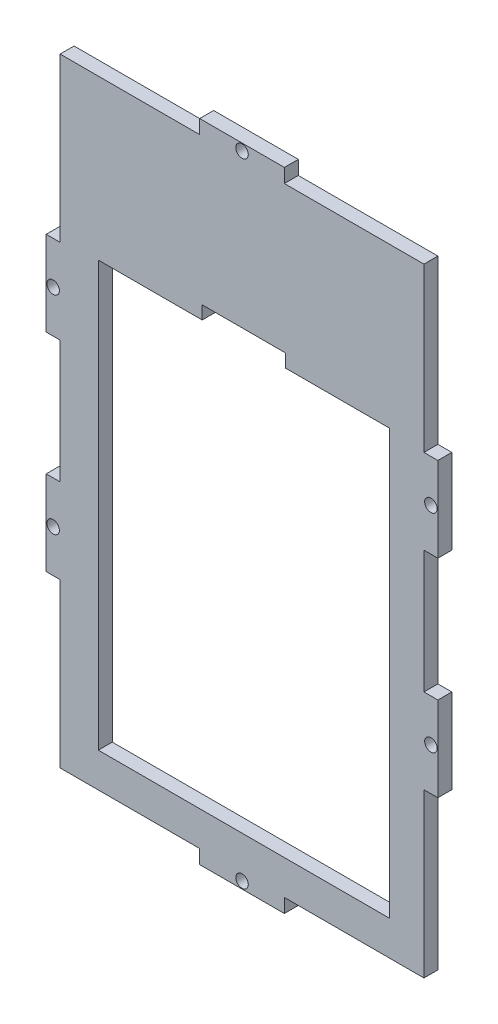
SolidWorks part; units mm, degrees
ref_plane "Front Plane" through (0, 0, 0) normal (0, 0, 1) x (1, 0, 0)
ref_plane "Top Plane" through (0, 0, 0) normal (0, 1, 0) x (1, 0, 0)
ref_plane "Right Plane" through (0, 0, 0) normal (1, 0, 0) x (0, 0, -1)
sketch "Sketch1" plane through (0, 0, 0) normal (0, 0, 1) x (1, 0, 0)
  line L0 (-41.465, 70.465) -> (-13.8217, 70.465)
  line L1 (-41.465, -70.465) -> (41.465, -70.465)
  line L2 (-41.465, -70.465) -> (-41.465, 70.465)
  line L3 (-41.465, 70.465) -> (41.465, 70.465) construction
  line L4 (41.465, -70.465) -> (41.465, 70.465)
  line L5 (-41.465, -70.465) -> (41.465, 70.465) construction
  line L6 (-41.465, 70.465) -> (41.465, -70.465) construction
  line L7 (-13.8217, 70.465) -> (13.8217, 70.465)
  line L8 (13.8217, 70.465) -> (41.465, 70.465)
  point P0 (0, 0)
  dimension "D1" = 82.93
  dimension "D2" = 140.93
extrude "Boss-Extrude1" add sketch "Sketch1" along normal blind 3.18
sketch "Sketch3" plane through (0, 0, 0) normal (0, 0, -1) x (-1, 0, 0)
  line L0 (-33.5967, 34.1533) -> (-33.5967, -62.5967)
  line L1 (-33.5967, -62.5967) -> (32.7533, -62.5967)
  line L2 (32.7533, -62.5967) -> (32.7533, 34.1533)
  line L3 (32.7533, 34.1533) -> (9.0783, 34.1533)
  line L4 (9.0783, 34.1533) -> (9.0783, 37.1533)
  line L5 (9.0783, 37.1533) -> (-9.9217, 37.1533)
  line L6 (-9.9217, 37.1533) -> (-9.9217, 34.1533)
  line L7 (-9.9217, 34.1533) -> (-33.5967, 34.1533)
  line L8 (32.7533, 43.1533) -> (-33.5967, 43.1533)
  line L9 (32.7533, -62.5967) -> (32.7533, 43.1533)
  line L10 (-33.5967, -62.5967) -> (32.7533, -62.5967)
  line L11 (-33.5967, 43.1533) -> (-33.5967, -62.5967)
  line L12 (-33.5967, -62.5967) -> (-33.5967, -70.465) construction
  line L13 (41.465, -70.465) -> (-41.465, -70.465) construction
  line L14 (-33.5967, -62.5967) -> (-41.465, -62.5967) construction
  line L15 (-41.465, -70.465) -> (-41.465, 70.465) construction
  dimension "D1" = 66.35
  dimension "D2" = 96.75
  dimension "D3" = 105.75
  dimension "D4" = 19
  dimension "D5" = 3
extrude "Cut-Extrude1" cut sketch "Sketch3" against normal through all contours L6 L7 L0 L1 L2 L3 L4 L5 region at (0.4217, -13.7828, 0)
sketch "Sketch9" plane through (-41.465, 0, 0) normal (-1, 0, 0) x (0, 0, 1)
  line L0 (0, 0) -> (3.18, 0) construction
  line L1 (0, 70.465) -> (0, -70.465) construction
  line L2 (3.18, 70.465) -> (3.18, -70.465) construction
  line L4 (0, -9.65) -> (3.18, -9.65)
  line L5 (0, -9.65) -> (0, 9.65)
  line L6 (0, 9.65) -> (3.18, 9.65)
  line L7 (3.18, -9.65) -> (3.18, 9.65)
  line L8 (0, -9.65) -> (3.18, 9.65) construction
  line L9 (0, 9.65) -> (3.18, -9.65) construction
  point P6 (1.59, 0)
  dimension "D1" = 19.3
extrude "Boss-Extrude4" [suppressed] add sketch "Sketch9" along normal blind 3.18
sketch "Sketch10" [suppressed] plane through (0, 0, 3.18) normal (0, 0, 1) x (1, 0, 0)
  line L0 (-43.055, 9.65) -> (-43.055, -9.65) construction
  line L1 (-44.645, 9.65) -> (-41.465, 9.65) construction
  line L2 (-44.645, -9.65) -> (-41.465, -9.65) construction
  circle A0 centre (-43.055, 0) radius 1.425
extrude "Cut-Extrude4" [suppressed] cut sketch "Sketch10" against normal through all
mirror "Mirror1" [suppressed] about plane through (0, 0, 0) normal (1, 0, 0)
sketch "Sketch18" plane through (41.465, 0, 0) normal (1, 0, 0) x (0, 0, -1)
  line L0 (0, 0) -> (-3.18, 0) construction
  line L1 (0, -70.465) -> (0, 70.465) construction
  line L2 (-3.18, -70.465) -> (-3.18, 70.465) construction
  line L4 (-3.18, -9.65) -> (0, -9.65)
  line L5 (-3.18, -9.65) -> (-3.18, 9.65)
  line L6 (-3.18, 9.65) -> (0, 9.65)
  line L7 (0, -9.65) -> (0, 9.65)
  line L8 (-3.18, -9.65) -> (0, 9.65) construction
  line L9 (-3.18, 9.65) -> (0, -9.65) construction
  point P6 (-1.59, 0)
  dimension "D1" = 19.3
extrude "Boss-Extrude8" [suppressed] add sketch "Sketch18" along normal blind 3.18
sketch "Sketch19" [suppressed] plane through (0, 0, 3.18) normal (0, 0, 1) x (1, 0, 0)
  line L0 (43.055, -9.65) -> (43.055, 9.65) construction
  line L1 (44.645, -9.65) -> (41.465, -9.65) construction
  line L2 (44.645, 9.65) -> (41.465, 9.65) construction
  circle A0 centre (43.055, 0) radius 1.425
extrude "Cut-Extrude8" [suppressed] cut sketch "Sketch19" against normal through all
mirror "Mirror2" [suppressed] about plane through (0, 0, 0) normal (1, 0, 0)
sketch "Sketch20" plane through (0, 0, 3.18) normal (0, 0, 1) x (1, 0, 0)
  line L0 (0, 70.465) -> (0, 0) construction
  line L1 (41.465, 70.465) -> (-41.465, 70.465) construction
  line L2 (-9.65, 70.465) -> (9.65, 70.465)
  line L3 (9.65, 70.465) -> (9.65, 67.285)
  line L4 (9.65, 67.285) -> (1.425, 67.285)
  line L5 (1.425, 67.285) -> (1.425, 59.485)
  line L6 (1.425, 59.485) -> (3.175, 59.485)
  line L7 (3.175, 59.485) -> (3.175, 57.105)
  line L8 (3.175, 57.105) -> (1.425, 57.105)
  line L9 (1.425, 57.105) -> (1.425, 51.485)
  line L10 (1.425, 51.485) -> (-1.425, 51.485)
  line L11 (-1.425, 51.485) -> (-1.425, 57.105)
  line L12 (-1.425, 57.105) -> (-3.175, 57.105)
  line L13 (-3.175, 57.105) -> (-3.175, 59.485)
  line L14 (-3.175, 59.485) -> (-1.425, 59.485)
  line L15 (-1.425, 59.485) -> (-1.425, 67.285)
  line L16 (-1.425, 67.285) -> (-9.65, 67.285)
  line L17 (-9.65, 67.285) -> (-9.65, 70.465)
  dimension "D1" = 19.3
  dimension "D2" = 3.18
  dimension "D3" = 15.8
  dimension "D4" = 6.35
  dimension "D5" = 2.38
  dimension "D6" = 2.85
  dimension "D7" = 7.8
extrude "Cut-Extrude9" [suppressed] cut sketch "Sketch20" against normal through all
mirror "Mirror3" [suppressed] about plane through (0, 0, 0) normal (0, 1, 0)
sketch "Sketch23" plane through (0, 0, 3.18) normal (0, 0, 1) x (1, 0, 0)
  line L0 (-41.465, 10.815) -> (-41.465, 30.115)
  line L1 (-41.465, 70.465) -> (-41.465, -70.465) construction
  line L2 (-41.465, 30.115) -> (-38.285, 30.115)
  line L3 (-38.285, 30.115) -> (-38.285, 21.89)
  line L4 (-38.285, 21.89) -> (-30.485, 21.89)
  line L5 (-30.485, 21.89) -> (-31.5806, 23.4685)
  line L6 (-31.5806, 23.4685) -> (-29.2006, 23.4685)
  line L7 (-29.2006, 23.4685) -> (-28.105, 21.89)
  line L8 (-28.105, 21.89) -> (-22.485, 21.89)
  line L9 (-22.485, 21.89) -> (-22.485, 19.04)
  line L10 (-22.485, 19.04) -> (-28.105, 19.04)
  line L11 (-28.105, 19.04) -> (-28.105, 17.1185)
  line L12 (-28.105, 17.1185) -> (-30.485, 17.1185)
  line L13 (-30.485, 17.1185) -> (-30.485, 19.04)
  line L14 (-30.485, 19.04) -> (-38.285, 19.04)
  line L15 (-38.285, 19.04) -> (-38.285, 10.815)
  line L16 (-38.285, 10.815) -> (-41.465, 10.815)
  line L17 (41.465, 70.465) -> (-41.465, 70.465) construction
  line L19 (-22.485, 20.465) -> (-41.465, 20.465) construction
  line L20 (-41.465, -30.115) -> (-41.465, -10.815)
  line L21 (-41.465, -10.815) -> (-38.285, -10.815)
  line L22 (-38.285, -10.815) -> (-38.285, -19.04)
  line L23 (-38.285, -19.04) -> (-30.485, -19.04)
  line L24 (-30.485, -19.04) -> (-30.485, -17.29)
  line L25 (-30.485, -17.29) -> (-28.105, -17.29)
  line L26 (-28.105, -17.29) -> (-28.105, -19.04)
  line L27 (-28.105, -19.04) -> (-22.485, -19.04)
  line L28 (-22.485, -19.04) -> (-22.485, -21.89)
  line L29 (-22.485, -21.89) -> (-28.105, -21.89)
  line L30 (-28.105, -21.89) -> (-28.105, -23.64)
  line L31 (-28.105, -23.64) -> (-30.485, -23.64)
  line L32 (-30.485, -23.64) -> (-30.485, -21.89)
  line L33 (-30.485, -21.89) -> (-38.285, -21.89)
  line L34 (-38.285, -21.89) -> (-38.285, -30.115)
  line L35 (-38.285, -30.115) -> (-41.465, -30.115)
  line L36 (-41.465, -20.465) -> (-22.485, -20.465) construction
  line L37 (-41.465, -70.465) -> (41.465, -70.465) construction
  dimension "D1" = 50
  dimension "D2" = 19.3
  dimension "D3" = 3.18
  dimension "D4" = 15.8
  dimension "D5" = 6.35
  dimension "D6" = 2.85
  dimension "D7" = 7.8
  dimension "D8" = 2.38
  dimension "D9" = 19.3
  dimension "D10" = 3.18
  dimension "D11" = 7.8
  dimension "D12" = 15.8
  dimension "D13" = 6.35
  dimension "D14" = 2.85
  dimension "D15" = 2.38
  dimension "D16" = 50
extrude "Cut-Extrude10" [suppressed] cut sketch "Sketch23" against normal through all
sketch "Sketch24" plane through (0, 0, 3.18) normal (0, 0, 1) x (1, 0, 0)
  line L0 (41.465, -10.815) -> (41.465, -30.115)
  line L1 (41.465, -70.465) -> (41.465, 70.465) construction
  line L2 (41.465, -30.115) -> (38.285, -30.115)
  line L3 (38.285, -30.115) -> (38.285, -21.89)
  line L4 (38.285, -21.89) -> (30.485, -21.89)
  line L5 (30.485, -21.89) -> (30.485, -23.64)
  line L6 (30.485, -23.64) -> (28.105, -23.64)
  line L7 (28.105, -23.64) -> (28.105, -21.89)
  line L8 (28.105, -21.89) -> (22.485, -21.89)
  line L9 (22.485, -21.89) -> (22.485, -19.04)
  line L10 (22.485, -19.04) -> (28.105, -19.04)
  line L11 (28.105, -19.04) -> (28.105, -17.29)
  line L12 (28.105, -17.29) -> (30.485, -17.29)
  line L13 (30.485, -17.29) -> (30.485, -19.04)
  line L14 (30.485, -19.04) -> (38.285, -19.04)
  line L15 (38.285, -19.04) -> (38.285, -10.815)
  line L16 (38.285, -10.815) -> (41.465, -10.815)
  line L17 (22.485, -20.465) -> (41.465, -20.465) construction
  line L18 (-41.465, -70.465) -> (41.465, -70.465) construction
  line L19 (41.465, 30.115) -> (41.465, 10.815)
  line L20 (41.465, 10.815) -> (38.285, 10.815)
  line L21 (38.285, 10.815) -> (38.285, 19.04)
  line L22 (38.285, 19.04) -> (30.485, 19.04)
  line L23 (30.485, 19.04) -> (30.485, 17.29)
  line L24 (30.485, 17.29) -> (28.105, 17.29)
  line L25 (28.105, 17.29) -> (28.105, 19.04)
  line L26 (28.105, 19.04) -> (22.485, 19.04)
  line L27 (22.485, 19.04) -> (22.485, 21.89)
  line L28 (22.485, 21.89) -> (28.105, 21.89)
  line L29 (28.105, 21.89) -> (28.105, 23.64)
  line L30 (28.105, 23.64) -> (30.485, 23.64)
  line L31 (30.485, 23.64) -> (30.485, 21.89)
  line L32 (30.485, 21.89) -> (38.285, 21.89)
  line L33 (38.285, 21.89) -> (38.285, 30.115)
  line L34 (38.285, 30.115) -> (41.465, 30.115)
  line L35 (22.485, 20.465) -> (41.465, 20.465) construction
  line L36 (41.465, 70.465) -> (-41.465, 70.465) construction
  dimension "D1" = 19.3
  dimension "D2" = 3.18
  dimension "D3" = 15.8
  dimension "D4" = 7.8
  dimension "D5" = 6.35
  dimension "D6" = 2.85
  dimension "D7" = 2.38
  dimension "D8" = 50
  dimension "D9" = 19.3
  dimension "D10" = 3.18
  dimension "D11" = 7.8
  dimension "D12" = 15.8
  dimension "D13" = 6.35
  dimension "D14" = 2.85
  dimension "D15" = 2.38
  dimension "D16" = 50
extrude "Cut-Extrude11" [suppressed] cut sketch "Sketch24" against normal through all
sketch "Sketch25" plane through (0, 0, 3.18) normal (0, 0, 1) x (1, 0, 0)
  line L0 (9.65, -70.465) -> (-9.65, -70.465)
  line L1 (-41.465, -70.465) -> (41.465, -70.465) construction
  line L2 (-9.65, -70.465) -> (-9.65, -67.285)
  line L3 (-9.65, -67.285) -> (-1.425, -67.285)
  line L4 (-1.425, -67.285) -> (-1.425, -59.485)
  line L5 (-1.425, -59.485) -> (-3.175, -59.485)
  line L6 (-3.175, -59.485) -> (-3.175, -57.105)
  line L7 (-3.175, -57.105) -> (-1.425, -57.105)
  line L8 (-1.425, -57.105) -> (-1.425, -51.485)
  line L9 (-1.425, -51.485) -> (1.425, -51.485)
  line L10 (1.425, -51.485) -> (1.425, -57.105)
  line L11 (1.425, -57.105) -> (3.175, -57.105)
  line L12 (3.175, -57.105) -> (3.175, -59.485)
  line L13 (3.175, -59.485) -> (1.425, -59.485)
  line L14 (1.425, -59.485) -> (1.425, -67.285)
  line L15 (1.425, -67.285) -> (9.65, -67.285)
  line L16 (9.65, -67.285) -> (9.65, -70.465)
  line L17 (0, -70.465) -> (0, 0) construction
  dimension "D1" = 19.3
  dimension "D2" = 3.18
  dimension "D3" = 15.8
  dimension "D4" = 7.8
  dimension "D5" = 6.35
  dimension "D6" = 2.85
  dimension "D7" = 2.38
extrude "Cut-Extrude12" [suppressed] cut sketch "Sketch25" against normal through all
sketch "Sketch26" plane through (0, 0, 3.18) normal (0, 0, 1) x (1, 0, 0)
  line L0 (-9.65, 70.465) -> (9.65, 70.465)
  line L1 (41.465, 70.465) -> (-41.465, 70.465) construction
  line L2 (9.65, 70.465) -> (9.65, 67.285)
  line L3 (9.65, 67.285) -> (1.425, 67.285)
  line L4 (1.425, 67.285) -> (1.425, 59.485)
  line L5 (1.425, 59.485) -> (3.175, 59.485)
  line L6 (3.175, 59.485) -> (3.175, 57.105)
  line L7 (3.175, 57.105) -> (1.425, 57.105)
  line L8 (1.425, 57.105) -> (1.425, 51.485)
  line L9 (1.425, 51.485) -> (-1.425, 51.485)
  line L10 (-1.425, 51.485) -> (-1.425, 57.105)
  line L11 (-1.425, 57.105) -> (-3.175, 57.105)
  line L12 (-3.175, 57.105) -> (-3.175, 59.485)
  line L13 (-3.175, 59.485) -> (-1.425, 59.485)
  line L14 (-1.425, 59.485) -> (-1.425, 67.285)
  line L15 (-1.425, 67.285) -> (-9.65, 67.285)
  line L16 (-9.65, 67.285) -> (-9.65, 70.465)
  line L17 (0, 70.465) -> (0, -4.4192) construction
  dimension "D1" = 19.3
  dimension "D2" = 3.18
  dimension "D3" = 7.8
  dimension "D4" = 15.8
  dimension "D5" = 6.35
  dimension "D6" = 2.85
  dimension "D7" = 2.38
extrude "Cut-Extrude13" [suppressed] cut sketch "Sketch26" against normal through all
mirror "Mirror4" [suppressed] about plane through (0, 0, 0) normal (1, 0, 0)
mirror "Mirror5" [suppressed] about plane through (0, 0, 0) normal (1, 0, 0)
mirror "Mirror6" [suppressed] about plane through (0, 0, 0) normal (0, 1, 0)
mirror "Mirror7" [suppressed] about plane through (0, 0, 0) normal (0, 1, 0)
sketch "Sketch27" plane through (-41.465, 0, 0) normal (-1, 0, 0) x (0, 0, 1)
  line L0 (0, -33.295) -> (0, -13.995)
  line L1 (0, 70.465) -> (0, -70.465) construction
  line L2 (0, -13.995) -> (3.18, -13.995)
  line L3 (3.18, 70.465) -> (3.18, -70.465) construction
  line L4 (3.18, -13.995) -> (3.18, -33.295)
  line L5 (3.18, -33.295) -> (0, -33.295)
  line L6 (3.18, -23.645) -> (0, -23.645) construction
  line L7 (3.18, -70.465) -> (0, -70.465) construction
  dimension "D1" = 19.3
  dimension "D2" = 46.82
extrude "Boss-Extrude9" add sketch "Sketch27" along normal blind 3.18
sketch "Sketch28" plane through (0, -70.465, 0) normal (0, -1, 0) x (1, 0, 0)
  line L0 (9.65, 0) -> (-9.65, 0)
  line L1 (-41.465, 0) -> (41.465, 0) construction
  line L2 (-9.65, 0) -> (-9.65, 3.18)
  line L3 (-41.465, 3.18) -> (41.465, 3.18) construction
  line L4 (-9.65, 3.18) -> (9.65, 3.18)
  line L5 (9.65, 3.18) -> (9.65, 0)
  line L6 (0, 0) -> (0, 3.18) construction
  dimension "D1" = 19.3
extrude "Boss-Extrude10" add sketch "Sketch28" along normal blind 3.18
sketch "Sketch29" plane through (0, 0, 3.18) normal (0, 0, 1) x (1, 0, 0)
  line L0 (-44.645, -23.645) -> (-37.3062, -23.645) construction
  line L1 (-44.645, -33.295) -> (-44.645, -13.995) construction
  line L2 (-43.055, -13.995) -> (-43.055, -33.295) construction
  line L3 (-44.645, -13.995) -> (-41.465, -13.995) construction
  line L4 (-44.645, -33.295) -> (-41.465, -33.295) construction
  circle A0 centre (-43.055, -23.645) radius 1.425
extrude "Cut-Extrude14" cut sketch "Sketch29" against normal through all
sketch "Sketch30" plane through (0, 0, 3.18) normal (0, 0, 1) x (1, 0, 0)
  line L0 (0, -73.645) -> (0, -66.2855) construction
  line L1 (9.65, -73.645) -> (-9.65, -73.645) construction
  line L2 (9.65, -72.055) -> (-9.65, -72.055) construction
  line L3 (9.65, -73.645) -> (9.65, -70.465) construction
  line L4 (-9.65, -73.645) -> (-9.65, -70.465) construction
  circle A0 centre (0, -72.055) radius 1.425
extrude "Cut-Extrude15" cut sketch "Sketch30" against normal through all
mirror "Mirror8" about plane through (0, 0, 0) normal (1, 0, 0) of "Cut-Extrude14", "Boss-Extrude9"
mirror "Mirror9" about plane through (0, 0, 0) normal (0, 1, 0) of "Cut-Extrude15", "Boss-Extrude10", "Mirror8"
